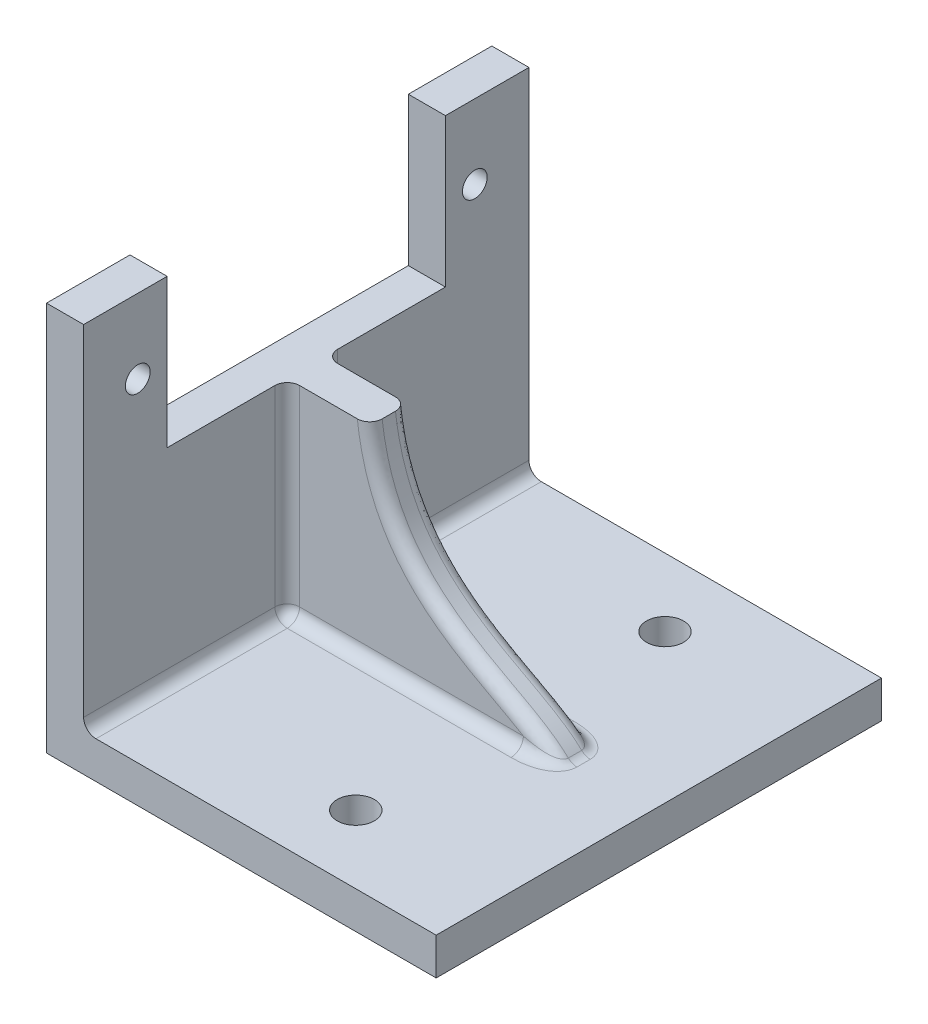
SolidWorks part; units mm, degrees
ref_plane "Front Plane" through (0, 0, 0) normal (0, 0, 1) x (1, 0, 0)
ref_plane "Top Plane" through (0, 0, 0) normal (0, 1, 0) x (1, 0, 0)
ref_plane "Right Plane" through (0, 0, 0) normal (1, 0, 0) x (0, 0, -1)
sketch "Sketch1" plane through (0, 0, 0) normal (0, 0, 1) x (1, 0, 0)
  line L0 (0, 0) -> (0, 30)
  line L1 (0, 0) -> (30, 0)
  dimension "D1" = 30
  dimension "D2" = 30
extrude "Extrude-Thin1" add sketch "Sketch1" along normal mid plane 36 thin thin type mid plane wall 3
sketch "Sketch3" plane through (-1.5, 0, 0) normal (-1, 0, 0) x (0, 0, 1)
  line L0 (0, 0) -> (0, 38.0242) construction
  line L1 (11.25, 30) -> (-11.25, 30)
  line L2 (11.25, 30) -> (11.25, 18)
  line L3 (11.25, 18) -> (-11.25, 18)
  line L4 (-11.25, 30) -> (-11.25, 18)
  line L5 (11.25, 30) -> (-11.25, 18) construction
  line L6 (11.25, 18) -> (-11.25, 30) construction
  line L7 (18, 30) -> (-18, 30) construction
  point P0 (0, 24)
  dimension "D1" = 12
  dimension "D2" = 22.5
extrude "Cut-Extrude1" cut sketch "Sketch3" against normal blind 10
sketch "Sketch4" plane through (1.5, 0, 0) normal (1, 0, 0) x (0, 0, -1)
  line L0 (0, 0) -> (0, 29.2251) construction
  line L8 (-11.25, 30) -> (-11.25, 18) construction
  circle A0 centre (-13.625, 24) radius 1
  circle A1 centre (13.625, 24) radius 1
  point P11 (-11.25, 24)
  dimension "D1" = 2
  dimension "D2" = 27.25
  dimension "D3" = 2
extrude "Cut-Extrude2" cut sketch "Sketch4" against normal blind 10
sketch "Sketch5" plane through (1.5, 0, 0) normal (1, 0, 0) x (0, 0, -1)
  line L0 (-11.25, 18) -> (11.25, 18) construction
  line L1 (1.5385, 1.5) -> (-1.5385, 1.5)
  line L2 (1.5385, 1.5) -> (1.5385, 18)
  line L3 (1.5385, 18) -> (-1.5385, 18)
  line L4 (-1.5385, 1.5) -> (-1.5385, 18)
  line L5 (1.5385, 1.5) -> (-1.5385, 18) construction
  line L6 (1.5385, 18) -> (-1.5385, 1.5) construction
  line L7 (-18, 1.5) -> (18, 1.5) construction
  point P0 (0, 9.75)
extrude "Boss-Extrude1" add sketch "Sketch5" along normal blind 22
sketch "Sketch6" plane through (0, 0, 1.5385) normal (0, 0, 1) x (1, 0, 0)
  line L0 (23.5, 18) -> (1.5, 18) construction
  line L1 (8.1709, 18) -> (23.5, 18)
  line L2 (23.5, 18) -> (23.5, 1.5)
  spline S0 degree 3 poles (8.1709, 18) (9.6059, 6.3077) (19.6988, 5.5915) (23.5, 1.5) knots 0 0 0 0 1 1 1 1
extrude "Cut-Extrude3" cut sketch "Sketch6" against normal blind 22
fillet "Fillet1" radius 1 9 edges at (1.5, 9.75, -1.5385) (1.5, 1.5, 9.7693) (1.5, 1.5, -9.7693) (12.5, 1.5, 1.5385) (1.5, 9.75, 1.5385)
sketch "Sketch7" plane through (0, 1.5, 0) normal (0, 1, 0) x (1, 0, 0)
  line L1 (0, 0) -> (42.0317, 0) construction
  circle A0 centre (18, -12.5) radius 1.5
  circle A1 centre (18, 12.5) radius 1.5
  dimension "D1" = 3
  dimension "D2" = 3
  dimension "D3" = 25
  dimension "D4" = 12
extrude "Cut-Extrude4" cut sketch "Sketch7" against normal blind 10
